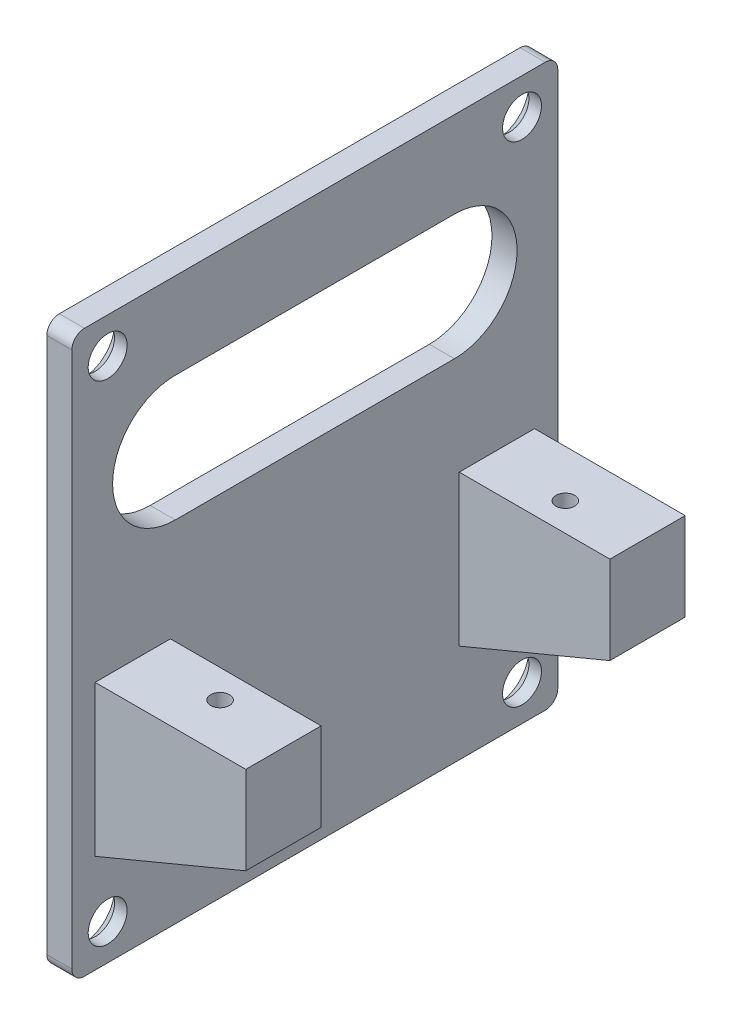
SolidWorks part; units mm, degrees
ref_plane "Front Plane" through (0, 0, 0) normal (0, 0, 1) x (1, 0, 0)
ref_plane "Top Plane" through (0, 0, 0) normal (0, 1, 0) x (1, 0, 0)
ref_plane "Right Plane" through (0, 0, 0) normal (1, 0, 0) x (0, 0, -1)
sketch "Sketch1" plane through (0, 0, 0) normal (1, 0, 0) x (0, 0, -1)
  line L0 (0, 0) -> (0, -50000) construction
  line L1 (19.5, 22.5) -> (-19.5, 22.5)
  line L2 (19.5, 22.5) -> (19.5, -22.5)
  line L3 (19.5, -22.5) -> (-19.5, -22.5)
  line L4 (-19.5, 22.5) -> (-19.5, -22.5)
  line L5 (19.5, 22.5) -> (-19.5, -22.5) construction
  line L6 (19.5, -22.5) -> (-19.5, 22.5) construction
  line L7 (-11.119, 10.5) -> (11.119, 10.5) construction
  line L8 (-11.119, 15.4897) -> (11.119, 15.4897)
  line L9 (-11.119, 5.5103) -> (11.119, 5.5103)
  circle A0 centre (-16.5, 19.5) radius 1.55
  circle A1 centre (16.5, 19.5) radius 1.55
  circle A2 centre (16.5, -19.5) radius 1.55
  arc A3 (-11.119, 15.4897) -> (-11.119, 5.5103) centre (-11.119, 10.5) ccw
  arc A4 (11.119, 5.5103) -> (11.119, 15.4897) centre (11.119, 10.5) ccw
  circle A5 centre (-16.5, -19.5) radius 1.55
  point P0 (0, 0)
  point P14 (0, -22.5)
  point P17 (0, 10.5)
  dimension "D9" = 3.1
  dimension "D10" = 3
  dimension "D12" = 12
  dimension "D1" = 45
  dimension "D2" = 39
  dimension "D3" = 3
  dimension "D4" = 3
  dimension "D5" = 3
  dimension "D6" = 3
  dimension "D7" = 3
  dimension "D8" = 3
  dimension "D11" = 3
extrude "Boss-Extrude1" add sketch "Sketch1" along normal blind 2 contours L1 L4 L3 L2 A2 A1 A0 region at (0, -2.212, 0)
sketch "Sketch2" plane through (2, 0, 0) normal (1, 0, 0) x (0, 0, -1)
  line L0 (0, 0) -> (0, -50000) construction
  line L1 (19.5, -22.5) -> (-19.5, -22.5) construction
  line L2 (17.5, -2.5) -> (11.5, -2.5)
  line L3 (17.5, -2.5) -> (17.5, -9.5)
  line L4 (17.5, -9.5) -> (11.5, -9.5)
  line L5 (11.5, -2.5) -> (11.5, -9.5)
  line L6 (17.5, -2.5) -> (11.5, -9.5) construction
  line L7 (17.5, -9.5) -> (11.5, -2.5) construction
  line L8 (-17.5, -9.5) -> (-11.5, -2.5) construction
  line L9 (-17.5, -2.5) -> (-11.5, -9.5) construction
  line L10 (-11.5, -2.5) -> (-11.5, -9.5)
  line L11 (-17.5, -9.5) -> (-11.5, -9.5)
  line L12 (-17.5, -2.5) -> (-17.5, -9.5)
  line L13 (-17.5, -2.5) -> (-11.5, -2.5)
  point P3 (14.5, -6)
  point P14 (-14.5, -6)
  dimension "D1" = 20
  dimension "D2" = 23
  dimension "D3" = 35
  dimension "D4" = 7
extrude "Boss-Extrude2" add sketch "Sketch2" along normal blind 12
chamfer "Chamfer1" distance 5 distance2 12 2 edges at (2, -9.5, -14.5) (2, -9.5, 14.5) first distance on face at (2, -19.5, 14.95)
sketch "Sketch3" plane through (0, -2.5, 0) normal (0, 1, 0) x (1, 0, 0)
  line L0 (8.2, 13.75) -> (8.2, -13.75) construction
  line L1 (0, 0) -> (8.2, 0) construction
  line L2 (2, 19.5) -> (2, -19.5) construction
  circle A0 centre (8.2, -13.75) radius 0.75
  circle A1 centre (8.2, 13.75) radius 0.75
  dimension "D2" = 1.5
  dimension "D1" = 27.5
  dimension "D3" = 6.2
extrude "Cut-Extrude1" cut sketch "Sketch3" against normal blind 22 and the other way blind 12
sketch "Sketch4" plane through (2, 0, 0) normal (1, 0, 0) x (0, 0, -1)
  line L0 (19.5, 22.5) -> (19.5, -22.5)
  line L1 (19.5, 22.5) -> (19.5, -22.5)
  line L2 (19.5, -22.5) -> (-19.5, -22.5)
  line L3 (19.5, -22.5) -> (-19.5, -22.5)
  line L4 (-19.5, -22.5) -> (-19.5, 22.5)
  line L5 (-19.5, -22.5) -> (-19.5, 22.5)
  line L6 (-19.5, 22.5) -> (19.5, 22.5)
  line L7 (-19.5, 22.5) -> (19.5, 22.5)
  line L8 (19.35, 22.35) -> (19.35, -22.35)
  line L9 (19.35, -22.35) -> (-19.35, -22.35)
  line L10 (-19.35, -22.35) -> (-19.35, 22.35)
  line L11 (-19.35, 22.35) -> (19.35, 22.35)
  dimension "D1" = 0.15
extrude "Cut-Extrude2" cut sketch "Sketch4" against normal through all both and the other way through all
fillet "Fillet1" radius 1 4 edges at (1, -22.35, 19.35) (1, -22.35, -19.35) (1, 22.35, 19.35) (1, 22.35, -19.35)
chamfer "Chamfer2" distance 1 angle 45 4 edges at (0, 19.5, 14.95) (0, 19.5, -18.05) (0, -19.5, -18.05) (0, -19.5, 14.95)
